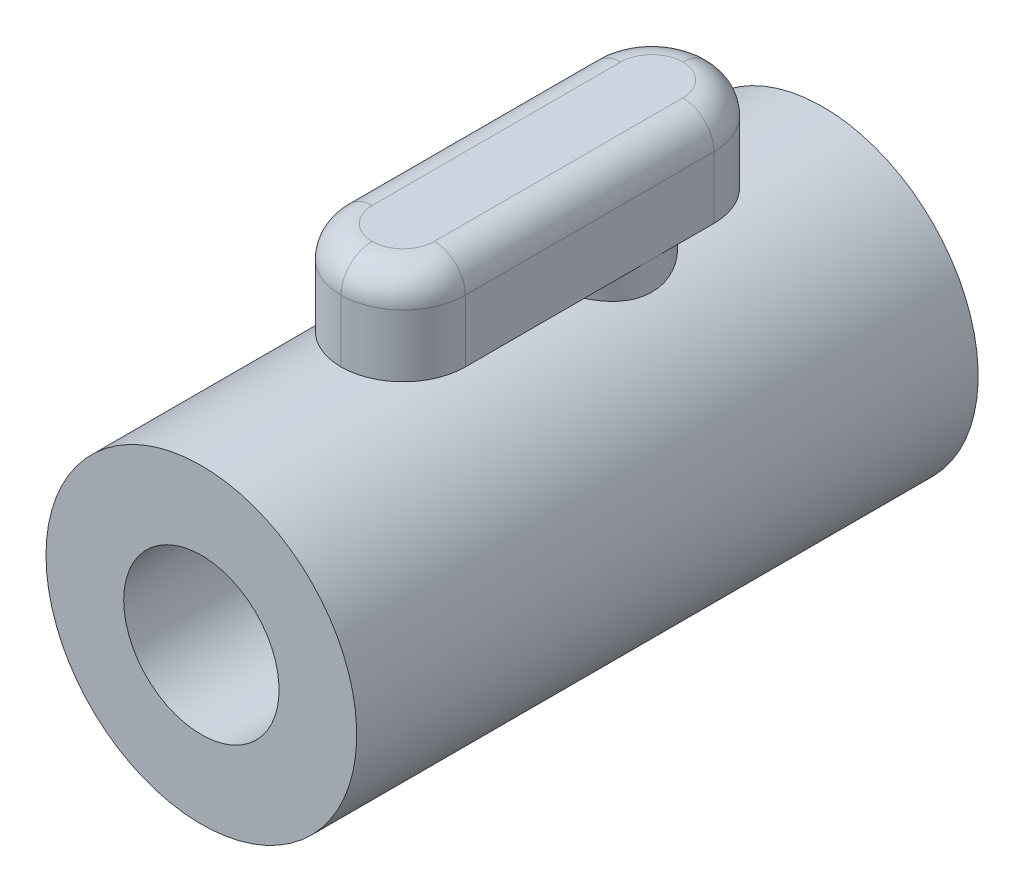
SolidWorks part; units mm, degrees
ref_plane "Front Plane" through (0, 0, 0) normal (0, 0, 1) x (1, 0, 0)
ref_plane "Top Plane" through (0, 0, 0) normal (0, 1, 0) x (1, 0, 0)
ref_plane "Right Plane" through (0, 0, 0) normal (1, 0, 0) x (0, 0, -1)
sketch "Sketch10" plane through (0, 0, 0) normal (0, 0, -1) x (-1, 0, 0)
  circle A0 centre (0, 0) radius 10
  dimension "D1" = 20
extrude "Extrude-Thin6" add sketch "Sketch10" along normal blind 40 from offset 10 separate body thin offset against normal yes thin type one direction reverse wall 5
ref_plane "Plane2" through (0, 15, 0) normal (0, 1, 0) x (1, 0, 0)
sketch "Sketch11" plane through (0, 15, 0) normal (0, 1, 0) x (1, 0, 0)
  circle A0 centre (0, 15) radius 4
  dimension "D1" = 8
  dimension "D2" = 15
extrude "Boss-Extrude3" add sketch "Sketch11" against normal up to next
sketch "Sketch12" plane through (0, 15, 0) normal (0, 1, 0) x (1, 0, 0)
  line L1 (0.2687, 18.991) -> (-4, 18.991)
  line L2 (0.2687, 18.991) -> (0.2687, 69.707)
  line L3 (0.2687, 69.707) -> (-4, 69.707)
  line L4 (-4, 18.991) -> (-4, 69.707)
  circle A0 centre (0, 15) radius 4 construction
  circle A1 centre (0, 15) radius 4 construction
extrude "Cut-Extrude2" cut sketch "Sketch12" against normal blind 4
sketch "Sketch13" plane through (0, 0, -18.991) normal (0, 0, -1) x (-1, 0, 0)
  line L1 (-4, 11) -> (4, 11)
  line L2 (-4, 11) -> (-4, 17)
  line L3 (-4, 17) -> (4, 17)
  line L4 (4, 11) -> (4, 17)
  point P5 (-0.2687, 11)
  point P6 (0, 0)
  dimension "D1" = 6
  dimension "D2" = 8
  dimension "D3" = 4
  dimension "D4" = 11
extrude "Boss-Extrude4" add sketch "Sketch13" along normal blind 24 from offset 20 offset against normal yes
fillet "Fillet3" radius 4 4 edges at (4, 14, -22.991) (-4, 14, 1.009) (4, 14, 1.009) (-4, 14, -22.991)
fillet "Fillet4" radius 2 6 edges at (-2.8284, 17, -21.8194) (2.8284, 17, -21.8194) (4, 17, -10.991) (2.8284, 17, -0.1625) (-2.8284, 17, -0.1625) (-4, 17, -10.991)
